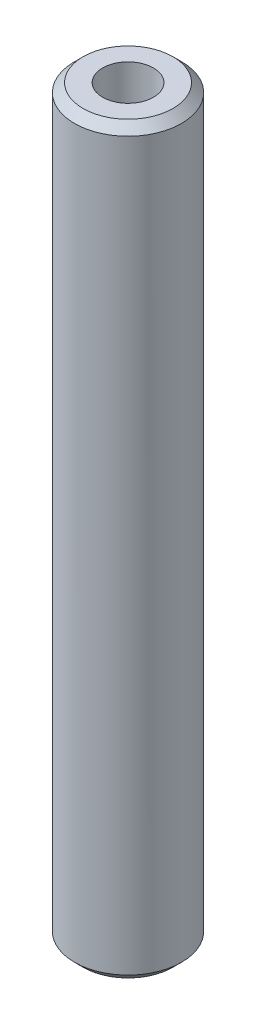
SolidWorks part; units mm, degrees
ref_plane "Front Plane" through (0, 0, 0) normal (0, 0, 1) x (1, 0, 0)
ref_plane "Top Plane" through (0, 0, 0) normal (0, 1, 0) x (1, 0, 0)
ref_plane "Right Plane" through (0, 0, 0) normal (1, 0, 0) x (0, 0, -1)
sketch "Sketch1" plane through (0, 0, 0) normal (0, 1, 0) x (1, 0, 0)
  circle A0 centre (0, 0) radius 22.5
  dimension "SHAFT_OD" = 45
extrude "Boss-Extrude1" add sketch "Sketch1" along normal blind 312.6066
sketch "Sketch2" plane through (0, 0, 0) normal (0, 1, 0) x (1, 0, 0)
  circle A0 centre (0, 0) radius 10.6817
  dimension "BORE_D" = 21.3634
extrude "Cut-Extrude1" cut sketch "Sketch2" along normal through all
chamfer "Chamfer1" distance 3.6262 angle 45 2 edges at (0, 312.6066, 22.5) (0, 0, 22.5)
